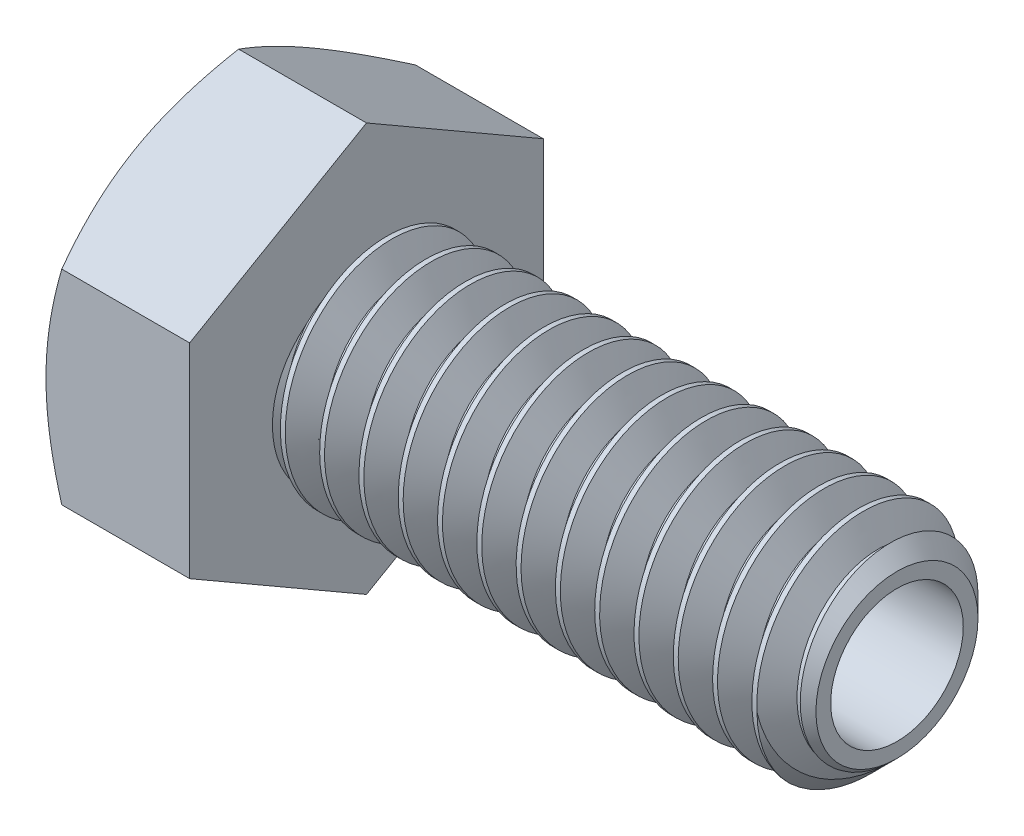
SolidWorks part; units mm, degrees
material "2024 Alloy"
ref_plane "Front Plane" through (0, 0, 0) normal (0, 0, 1) x (1, 0, 0)
ref_plane "Top Plane" through (0, 0, 0) normal (0, 1, 0) x (1, 0, 0)
ref_plane "Right Plane" through (0, 0, 0) normal (1, 0, 0) x (0, 0, -1)
sketch "Sketch1" plane through (0, 0, 0) normal (0, 0, 1) x (1, 0, 0)
  line L0 (-12.1047, 0) -> (12.1047, 0) construction
  line L1 (12.1047, 3.9688) -> (12.1047, -3.9688) construction
  line L2 (-6.9453, 6.35) -> (-6.9453, -6.35) construction
  line L3 (-12.1047, 6.35) -> (-12.1047, -6.35) construction
  point P9 (-6.9453, 0)
  point P10 (7.1658, -3.9688)
  dimension "D1" = 4.9389
  dimension "Screw Dia" = 7.9375
  dimension "Hex" = 12.7
  dimension "Head Ht" = 5.1594
  dimension "Screw Lenght" = 19.05
ref_plane "Plane2" through (12.1047, 0, 0) normal (1, 0, 0) x (0, 0, -1)
sketch "Sketch5" plane through (12.1047, 0, 0) normal (1, 0, 0) x (0, 0, -1)
  circle A0 centre (0, 0) radius 3.9688
extrude "Boss-Extrude3" add sketch "Sketch5" against normal up to vertex (19.05 mm away) up to point (-6.9453, 0, 0)
sketch "Sketch9" plane through (12.1047, 0, 0) normal (1, 0, 0) x (0, 0, -1)
  circle A1 centre (0, 0) radius 3.9688
  circle A2 centre (0, 0) radius 3.9688
  dimension "D1" = 0
curve "Helix/Spiral1" pitch 1.4111 height 20.4611 turns 14.5 parameters "Pitch"=1.4111
chamfer "Chamfer1" distance 1.0583 angle 45 1 edges at (12.1047, 0, -3.9688)
sketch "Sketch10" plane through (0, 0, 0) normal (0, 0, 1) x (1, 0, 0)
  line L0 (12.1047, 3.9688) -> (12.6339, 3.0522)
  line L1 (12.6339, 3.0522) -> (12.8102, 3.0522)
  line L2 (12.8102, 3.0522) -> (13.3394, 3.9688)
  line L3 (12.1047, 3.9688) -> (13.3394, 3.9688)
  line L4 (12.722, 3.9688) -> (12.722, 3.0522) construction
  line L5 (12.3693, 3.5105) -> (13.0748, 3.5105) construction
  dimension "D1" = 60
  dimension "D2" = 0.1764
  dimension "D3" = 0.7056
sweep "Cut-Sweep1" cut profiles "Sketch10" path "Helix/Spiral1" align with end faces yes
sketch "Sketch6" plane through (-6.9453, 0, 0) normal (-1, 0, 0) x (0, 0, 1)
  line L0 (0, 6.35) -> (0, -6.35) construction
  line L1 (6.35, 3.6662) -> (0, 7.3323)
  line L2 (0, 7.3323) -> (-6.35, 3.6662)
  line L3 (-6.35, 3.6662) -> (-6.35, -3.6662)
  line L4 (-6.35, -3.6662) -> (0, -7.3323)
  line L5 (0, -7.3323) -> (6.35, -3.6662)
  line L6 (6.35, -3.6662) -> (6.35, 3.6662)
  circle A0 centre (0, 0) radius 6.35 construction
extrude "Boss-Extrude4" add sketch "Sketch6" along normal up to vertex (5.1594 mm away) up to point (-12.1047, -6.35, 0)
sketch "Sketch7" plane through (-12.1047, 0, 0) normal (-1, 0, 0) x (0, 0, 1)
  circle A0 centre (0, 0) radius 6.35 construction
  circle A1 centre (0, 0) radius 6.35
sketch "Sketch8" plane through (-12.1047, 0, 0) normal (-1, 0, 0) x (0, 0, 1)
  circle A0 centre (0, 0) radius 6.35 construction
  circle A1 centre (0, 0) radius 6.35
extrude "Cut-Extrude3" cut sketch "Sketch8" against normal through all draft 60 flip side to cut
sketch "Sketch11" plane through (12.1047, 0, 0) normal (1, 0, 0) x (0, 0, -1)
  circle A0 centre (0, 0) radius 2.3813
  point P2 (0, 0)
  point P3 (0, 0)
  dimension "D1" = 4.7625
extrude "Cut-Extrude4" cut sketch "Sketch11" against normal offset from surface (21.0344 mm away) 3.175 up to face at (-12.1047, 0, 0)
equation "\"D2@Sketch10\" = \"Pitch@Helix/Spiral1\"*.125"
equation "\"D3@Sketch10\" = \"Pitch@Helix/Spiral1\"*.5"
equation "\"D3@Helix/Spiral1\" = \"Screw Lenght@Sketch1\"+\"Pitch@Helix/Spiral1\""
equation "\"D1@Chamfer1\" = \"Pitch@Helix/Spiral1\"*.75"
equation "\"D1@Sketch1\" = \"Pitch@Helix/Spiral1\"*3.5"
